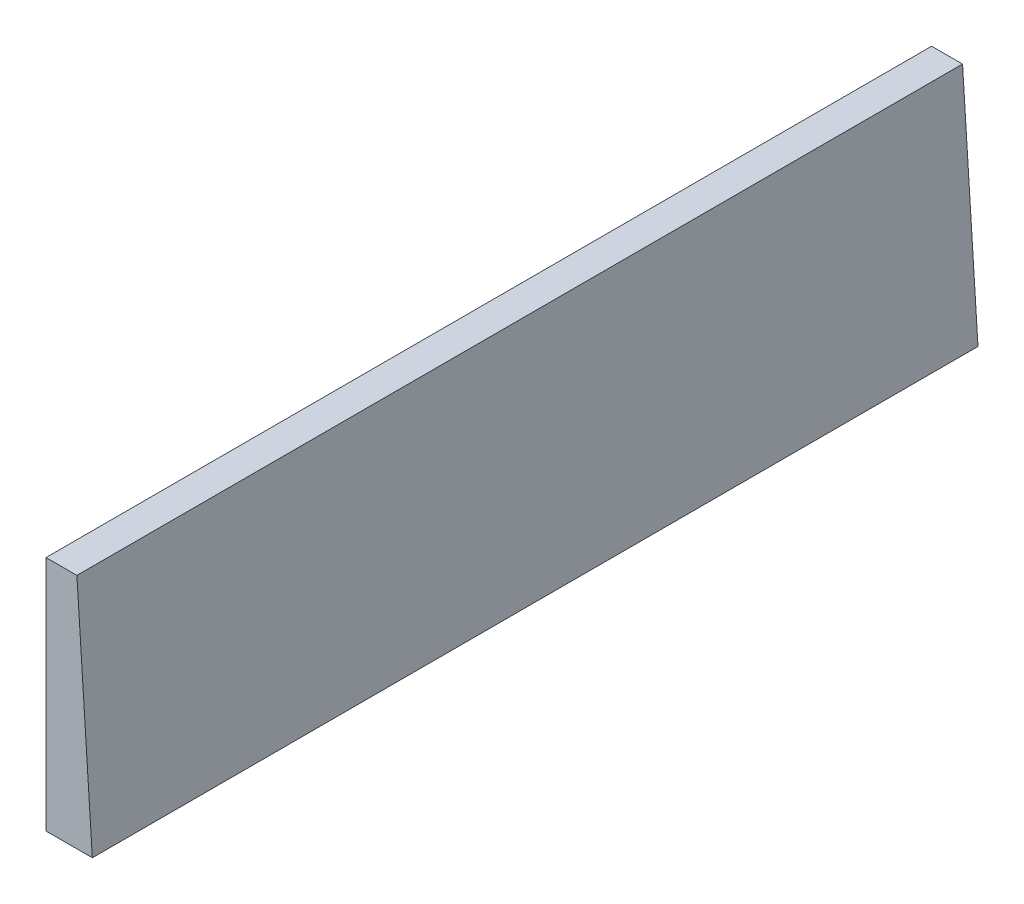
SolidWorks part; units mm, degrees
ref_plane "Front Plane" through (0, 0, 0) normal (0, 0, 1) x (1, 0, 0)
ref_plane "Top Plane" through (0, 0, 0) normal (0, 1, 0) x (1, 0, 0)
ref_plane "Right Plane" through (0, 0, 0) normal (1, 0, 0) x (0, 0, -1)
sketch "Sketch1" plane through (0, 0, 0) normal (0, 0, 1) x (1, 0, 0)
  line L0 (0, 0) -> (0, 1150)
  line L1 (0, 1150) -> (300, 1150)
  line L2 (0, 0) -> (0, -1150)
  line L3 (0, -1150) -> (450, -1150)
  line L4 (450, -1150) -> (300, 1150)
  dimension "D1" = 1150
  dimension "D2" = 300
  dimension "D3" = 450
extrude "Boss-Extrude1" add sketch "Sketch1" along normal blind 4300 and the other way blind 4300
